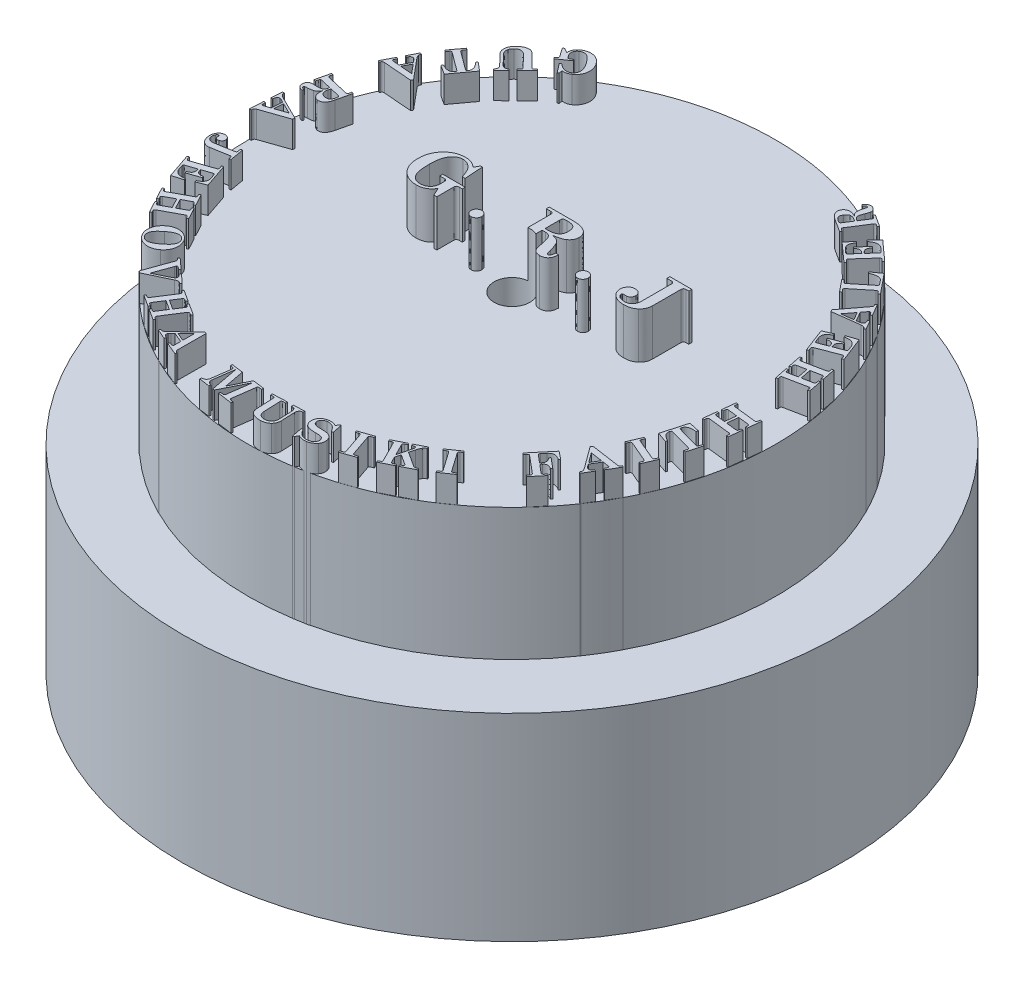
SolidWorks part; units mm, degrees
material "1100-H16 Rod (SS)"
ref_plane "Front Plane" through (0, 0, 0) normal (0, 0, 1) x (1, 0, 0)
ref_plane "Top Plane" through (0, 0, 0) normal (0, 1, 0) x (1, 0, 0)
ref_plane "Right Plane" through (0, 0, 0) normal (1, 0, 0) x (0, 0, -1)
sketch "Sketch1" plane through (0, 0, 0) normal (0, 1, 0) x (1, 0, 0)
  circle A0 centre (0, 0) radius 50
  dimension "D1" = 100
extrude "Boss-Extrude1" add sketch "Sketch1" along normal blind 30
sketch "Sketch2" plane through (0, 30, 0) normal (0, 1, 0) x (1, 0, 0)
  circle A0 centre (0, 0) radius 40
  dimension "D1" = 80
extrude "Boss-Extrude2" add sketch "Sketch2" along normal blind 20
sketch "Sketch3" plane through (0, 50, 0) normal (0, 1, 0) x (1, 0, 0)
  circle A0 centre (0, 0) radius 40 construction
  circle A1 centre (0, 0) radius 40 construction
  spline S0 degree 3 poles (-12.1045, 38.4852) (-22.9661, 33.7232) (-34.3652, 23.0084) (-40.7901, 6.3446) (-39.5886, -11.7966) (-30.7259, -27.8008) (-14.0017, -39.3813) (6.6013, -41.2874) (24.7101, -33.1093) (36.9035, -18.8732) (40.8288, -3.1811) (39.2765, 9.0746) (36.0934, 18.0804) (30.6234, 26.5636) (23.3392, 32.8785) (15.1021, 37.3668) (6.5682, 39.9026) (-2.9906, 40.2144) (-12.1045, 38.4852) (-22.9661, 33.7232) (-34.3652, 23.0084) knots -0.110772 -0.072498 -0.040287 0 0.068677 0.141723 0.207124 0.281369 0.35355 0.443747 0.51626 0.584443 0.662545 0.70228 0.731598 0.776773 0.821939 0.845824 0.889228 0.927502 0.959713 1 1.068677 1.141723 1.207124 only from (-20.5688, 34.3063) to (-20.5688, 34.3063)
sketch "Sketch5" plane through (0, 50, 0) normal (0, 1, 0) x (1, 0, 0)
  line L0 (-18.1368, 0) -> (22.4426, 0)
sketch "Sketch6" plane through (0, 30, 0) normal (0, 1, 0) x (1, 0, 0)
  text T0 "G U T A   R A   J E H O V H A   M U S I K I    F A I T H    H E A L E R " font "Century Schoolbook" height 4.4
extrude "Boss-Extrude3" add sketch "Sketch6" along normal blind 24
sketch "Sketch7" plane through (0, 50, 0) normal (0, 1, 0) x (1, 0, 0)
  text T0 "G . R . J" font "Century Schoolbook" height 7
extrude "Boss-Extrude4" add sketch "Sketch7" along normal blind 7
sketch "Sketch8" plane through (0, 0, 0) normal (0, -1, 0) x (1, 0, 0)
  circle A0 centre (0, 0) radius 38.7151
extrude "Cut-Extrude1" cut sketch "Sketch8" against normal blind 10
sketch "Sketch9" plane through (0, 10, 0) normal (0, -1, 0) x (1, 0, 0)
  circle A0 centre (0, 0) radius 2.7068
extrude "Cut-Extrude2" cut sketch "Sketch9" against normal through all
